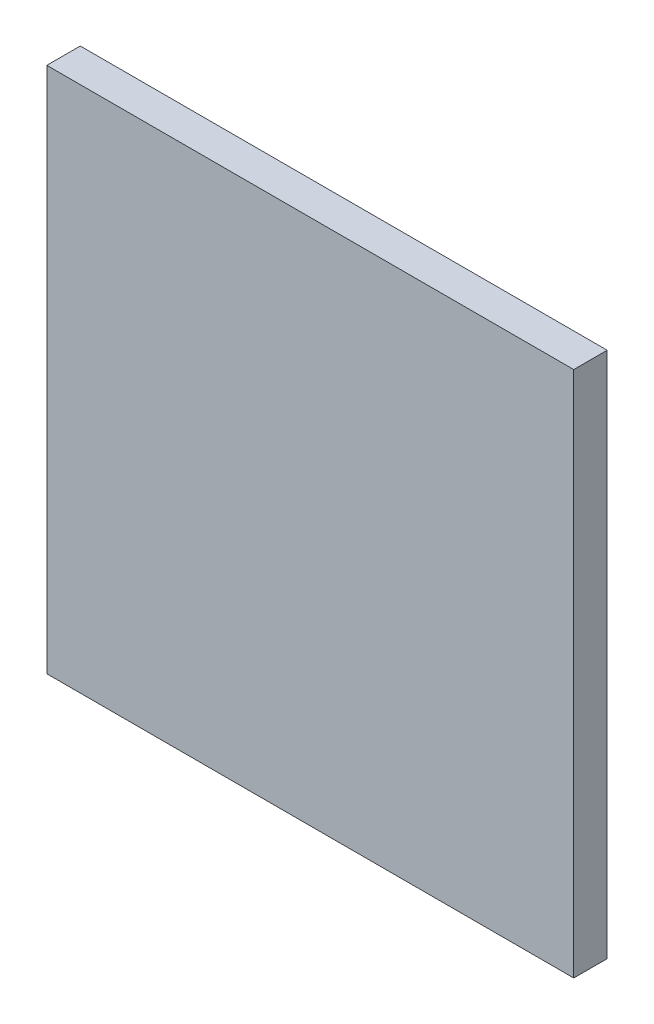
SolidWorks part; units mm, degrees
ref_plane "Front Plane" through (0, 0, 0) normal (0, 0, 1) x (1, 0, 0)
ref_plane "Top Plane" through (0, 0, 0) normal (0, 1, 0) x (1, 0, 0)
ref_plane "Right Plane" through (0, 0, 0) normal (1, 0, 0) x (0, 0, -1)
sketch "Sketch1" plane through (0, 0, 0) normal (0, 0, 1) x (1, 0, 0)
  line L1 (-3.15, -3.15) -> (3.15, -3.15)
  line L2 (-3.15, -3.15) -> (-3.15, 3.15)
  line L3 (-3.15, 3.15) -> (3.15, 3.15)
  line L4 (3.15, -3.15) -> (3.15, 3.15)
  line L5 (-3.15, -3.15) -> (3.15, 3.15) construction
  line L6 (-3.15, 3.15) -> (3.15, -3.15) construction
  point P0 (0, 0)
  dimension "D1" = 6.3
  dimension "D2" = 6.3
extrude "chip" add sketch "Sketch1" along normal blind 0.4
equation "\"pcb_length\"= 40 ' length of the chip in the direction of the feadline"
equation "\"pcb_side\"= 20    ' length of the chip in the other direction"
equation "\"pcb_width\"= 1"
equation "\"wall_width\"= 1  ' minimal width from the box walls"
equation "\"route_width\"= 1 ' The width of the trace on the lid for not touching the signal roates."
equation "\"route_clearence\"= 0.4 ' The clearence depth of the trace on the lid for not touching the signal roates."
equation "\"route_chip_clearence\"= 1"
equation "\"port_count\"= 2"
equation "\"port_space\"= 1.5"
equation "\"port_length\"= 5.1"
equation "\"port_width\"= 5.1"
equation "\"chip_length\"= 6.3 ' length of the chip in the direction of the feadline"
equation "\"chip_side\"= 6.3 ' length of the chip in the other direction"
equation "\"chip_width\"= 0.4 ' width of the chip"
equation "\"pedestal_depth\"= 1 ' depth of the pedestal under the chip"
equation "\"chip_leg\"= 0.8  ' size of the legs the chip lay on in case there is pedestal"
equation "\"wing_length\"= 10 ' Mounting wing size"
equation "\"wing_width\"= 1 ' mounting wing width"
equation "\"bonding_clearence\"= 1"
equation "\"box_height\"= \"wall_width\" + \"pedestal_depth\" + \"pcb_width\""
equation "\"box_length\"= \"pcb_length\" + 2 * \"wall_width\""
equation "\"box_side\"= \"pcb_side\" + 2 * \"wall_width\""
equation "\"D1@Sketch1\"=\"chip_length\""
equation "\"D2@Sketch1\"=\"chip_side\""
equation "\"D1@chip\" = \"chip_width\""
